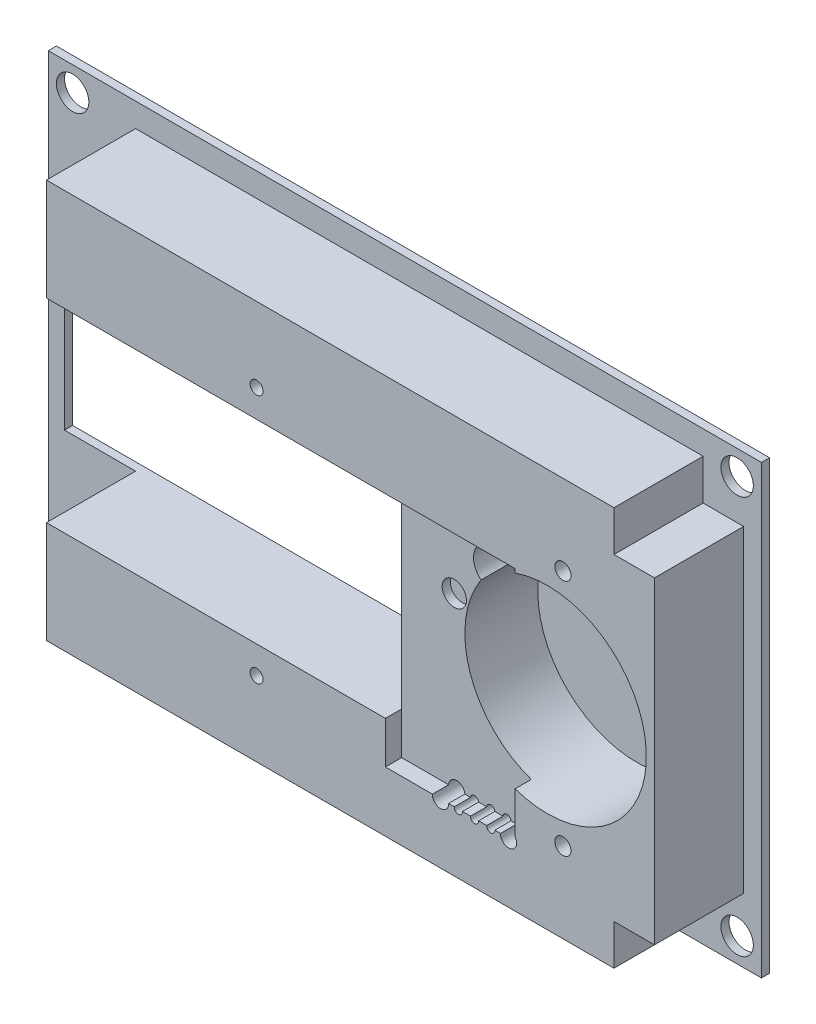
SolidWorks part; units mm, degrees
ref_plane "前视基准面" through (0, 0, 0) normal (0, 0, 1) x (1, 0, 0)
ref_plane "上视基准面" through (0, 0, 0) normal (0, 1, 0) x (1, 0, 0)
ref_plane "右视基准面" through (0, 0, 0) normal (1, 0, 0) x (0, 0, -1)
other "Configuration Table"
sketch "草图1" plane through (0, 0, 0) normal (0, 0, 1) x (1, 0, 0)
  line L9 (-75.0276, 24.608) -> (0, 24.608)
  line L10 (-75.0276, 24.608) -> (-75.0276, -24.608)
  line L16 (-75.0276, -24.608) -> (0, -24.608)
  line L17 (0, 24.608) -> (0, -24.608)
extrude "凸台-拉伸1" add sketch "草图1" along normal blind 11 contours L16 L17 L9 L10
sketch "草图2" plane through (0, 0, 0) normal (0, 0, -1) x (-1, 0, 0)
  line L5 (75.0276, 24.608) -> (75.0276, -24.608) construction
  line L6 (0, 24.608) -> (5, 24.608)
  line L7 (0, 24.608) -> (0, 19.608)
  line L8 (0, 19.608) -> (5, 19.608)
  line L9 (5, 24.608) -> (5, 19.608)
  line L10 (0, -24.608) -> (5, -24.608)
  line L11 (0, -24.608) -> (0, -19.608)
  line L12 (0, -19.608) -> (5, -19.608)
  line L13 (5, -24.608) -> (5, -19.608)
  line L14 (75.0276, 12) -> (33.2, 12)
  line L15 (75.0276, 12) -> (75.0276, -12)
  line L16 (75.0276, -12) -> (33.2, -12)
  line L17 (33.2, 12) -> (33.2, -12)
  line L18 (33.2, 0) -> (13.2, 0) construction
  line L21 (0, 24.608) -> (0, -24.608) construction
  circle A0 centre (13.2, 0) radius 12.2
  circle A1 centre (11.3, 14.7) radius 1
  circle A2 centre (11.3, -14.7) radius 1
  circle A4 centre (39.9, -2.2) radius 1.5
  circle A5 centre (55.8, 0) radius 1.5
  circle A6 centre (26.7, 3.6) radius 1.5
  circle A9 centre (49.1, 15.4) radius 0.8
  circle A10 centre (49.1, -15.4) radius 0.8
  dimension "D1" = 24.4
  dimension "D2" = 2
  dimension "D3" = 3
  dimension "D4" = 1.6
  dimension "D5" = 5
  dimension "D6" = 24
  dimension "D7" = 33.2
extrude "切除-拉伸1" cut sketch "草图2" along normal blind 3 from surface contours A1 | A2 | A6 | A9 | A10 starting at face at (-37.5138, 0, 11)
extrude "切除-拉伸3" cut sketch "草图2<4>" against normal through all contours L13 L12 L11 L10 | A0 | L16 L17 L14 L15 | L8 L9 L6 L7
sketch "草图2<4>" plane through (0, 0, 0) normal (0, 0, -1) x (-1, 0, 0) same geometry as "草图2"
sketch "草图4" plane through (0, 0, 0) normal (0, 0, -1) x (-1, 0, 0)
  line L1 (-2.2, 27.55) -> (85.8, 27.55)
  line L2 (-2.2, 27.55) -> (-2.2, -27.55)
  line L3 (-2.2, -27.55) -> (85.8, -27.55)
  line L4 (85.8, 27.55) -> (85.8, -27.55)
  line L5 (33.2, 12) -> (83.8, 12)
  line L6 (33.2, 12) -> (33.2, -12)
  line L7 (33.2, -12) -> (83.8, -12)
  line L8 (83.8, 12) -> (83.8, -12)
  circle A0 centre (0.8, 24.55) radius 2
  circle A1 centre (0.8, -24.55) radius 2
  circle A2 centre (82.8, -24.55) radius 2
  circle A3 centre (82.8, 24.55) radius 2
  dimension "D1" = 4
  dimension "D2" = 2
extrude "凸台-拉伸2" add sketch "草图4" along normal blind 1 contours L3 L4 L1 L2 | A1 | A0 | A3 | A2 | L6 L7 L8 L5
sketch "草图5" plane through (0, 0, 11) normal (0, 0, 1) x (1, 0, 0)
  line L0 (-21.8267, 8.6267) -> (-13.2, 0)
  line L1 (-13.2, 0) -> (-13.2, 35.0879) construction
  circle A0 centre (-21.8267, 8.6267) radius 2.5
  circle A1 centre (-13.2, 0) radius 12.2 construction
  dimension "D2" = 5
  dimension "D1" = 45
extrude "切除-拉伸4" cut sketch "草图5" against normal through all contours A0
sketch "草图7" plane through (0, 0, -1) normal (0, 0, -1) x (-1, 0, 0)
  line L0 (-2.2, 27.55) -> (-2.2, -27.55) construction
  line L1 (17.6, -14.75) -> (26.8, -14.75)
  line L2 (17.6, -14.75) -> (17.6, -19.75)
  line L3 (17.6, -19.75) -> (26.8, -19.75)
  line L4 (26.8, -14.75) -> (26.8, -19.75)
  line L5 (-2.2, -27.55) -> (85.8, -27.55) construction
  dimension "D1" = 9.2
  dimension "D2" = 19.8
  dimension "D3" = 7.8
  dimension "D4" = 5
extrude "切除-拉伸6" cut sketch "草图7" against normal blind 2
sketch "草图8" plane through (0, 0, 11) normal (0, 0, 1) x (1, 0, 0)
  circle A0 centre (-26.4, -17.25) radius 1
  circle A1 centre (-24.2, -17.25) radius 0.5
  circle A2 centre (-22.2, -17.25) radius 0.5
  circle A3 centre (-20.2, -17.25) radius 0.5
  circle A4 centre (-18, -17.25) radius 1
  dimension "D1" = 2
  dimension "D2" = 1
extrude "切除-拉伸7" cut sketch "草图8" against normal through all contours A0 | A1 | A2 | A3 | A4
sketch "草图9" plane through (0, 0, 11) normal (0, 0, 1) x (1, 0, 0)
  line L0 (-75.0276, -12) -> (-33.2, -12) construction
  line L1 (-33.2, 12) -> (-17.2, 12)
  line L2 (-33.2, 12) -> (-33.2, -17.2)
  line L3 (-33.2, -17.2) -> (-17.2, -17.2)
  line L4 (-17.2, 12) -> (-17.2, -17.2)
  dimension "D1" = 16
  dimension "D2" = 5.2
extrude "切除-拉伸8" cut sketch "草图9" against normal blind 2 contours L3 L4 L1 L2
